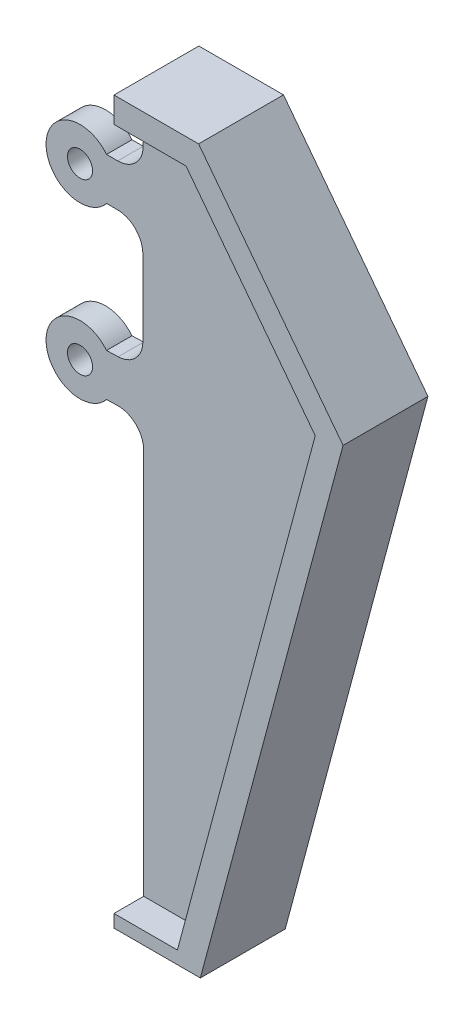
SolidWorks part; units mm, degrees
ref_plane "Front Plane" through (0, 0, 0) normal (0, 0, 1) x (1, 0, 0)
ref_plane "Top Plane" through (0, 0, 0) normal (0, 1, 0) x (1, 0, 0)
ref_plane "Right Plane" through (0, 0, 0) normal (1, 0, 0) x (0, 0, -1)
sketch "Sketch1" plane through (0, 0, 0) normal (0, 0, 1) x (1, 0, 0)
  line L0 (57.8544, 21.5204) -> (66.3427, 21.5204)
  line L1 (66.3427, 21.5204) -> (81.5634, 1.6159)
  line L2 (81.5634, 1.6159) -> (64.9249, -60.4796)
  line L9 (57.8544, 24.5204) -> (67.8253, 24.5204)
  line L11 (67.8253, 24.5204) -> (84.8432, 2.2654)
  line L16 (84.8432, 2.2654) -> (68.0307, -60.4796)
  line L26 (57.8544, 21.5204) -> (57.8544, 24.5204)
  line L27 (64.9249, -60.4796) -> (68.0307, -60.4796)
  line L29 (54.896, 24.5204) -> (67.8253, 24.5204) construction
  line L30 (54.7981, 17.5204) -> (54.896, 24.5204) construction
  line L31 (50.4769, 17.5204) -> (54.7981, 17.5204) construction
  line L32 (50.4769, 6.5204) -> (50.4769, 17.5204) construction
  line L33 (54.7565, 6.5204) -> (50.4769, 6.5204) construction
  line L34 (54.7565, -2.4381) -> (54.7565, 6.5204) construction
  line L35 (50.4769, -2.5721) -> (54.7565, -2.4381) construction
  line L36 (50.4769, -13.5447) -> (50.4769, -2.5721) construction
  line L37 (54.8544, -63.4796) -> (54.8544, -13.4508) construction
  line L38 (54.8544, -13.4508) -> (50.4769, -13.5447) construction
  line L39 (84.8432, 2.2654) -> (67.2269, -63.4796) construction
  line L40 (67.2269, -63.4796) -> (54.8544, -63.4796) construction
  line L41 (57.7565, -5.3456) -> (57.7565, 9.5204) construction
  line L42 (53.4769, -5.4796) -> (57.7565, -5.3456) construction
  line L43 (57.7565, 9.5204) -> (53.4769, 9.5204) construction
  line L44 (57.8544, -10.3857) -> (53.4769, -10.4796) construction
  line L45 (57.8544, -60.4796) -> (57.8544, -10.3857) construction
  line L46 (53.4769, -10.4796) -> (53.4769, -5.4796) construction
  line L47 (57.7565, 14.5204) -> (57.8544, 21.5204) construction
  line L48 (53.4769, 9.5204) -> (53.4769, 14.5204) construction
  line L49 (53.4769, 14.5204) -> (57.7565, 14.5204) construction
  line L50 (64.9249, -60.4796) -> (57.8544, -60.4796) construction
extrude "Boss-Extrude4" add sketch "Sketch1" along normal blind 5 and the other way blind 5
sketch "Sketch4" plane through (0, 0, 0) normal (0, 0, 1) x (1, 0, 0)
  line L0 (57.8542, 21.5184) -> (66.3426, 21.5184)
  line L1 (66.3426, 21.5184) -> (81.5632, 1.6139)
  line L2 (81.5632, 1.6139) -> (64.9248, -60.4816)
  line L3 (64.9248, -60.4816) -> (57.8542, -60.4816)
  line L4 (57.8542, -60.4816) -> (57.8542, -13.4528)
  line L6 (54.7899, -10.4534) -> (53.4767, -10.4816)
  line L8 (53.4767, -5.4816) -> (54.8502, -5.4386)
  line L10 (57.7563, -2.4401) -> (57.7563, 6.5184)
  line L12 (54.7563, 9.5184) -> (53.4767, 9.5184)
  line L14 (53.4767, 14.5184) -> (54.798, 14.5184)
  line L15 (57.7977, 17.4764) -> (57.8542, 21.5184)
  arc A0 (53.4767, 14.5184) -> (53.4767, 9.5184) centre (50.3542, 12.0184) ccw
  arc A1 (53.4767, -5.4816) -> (53.4767, -10.4816) centre (50.3542, -7.9816) ccw
  arc A2 (57.8542, -13.4528) -> (54.7899, -10.4534) centre (54.8542, -13.4528) ccw
  arc A3 (57.7563, -2.4401) -> (54.8502, -5.4386) centre (54.7563, -2.4401) cw
  arc A4 (57.7563, 6.5184) -> (54.7563, 9.5184) centre (54.7563, 6.5184) ccw
  arc A5 (54.798, 14.5184) -> (57.7977, 17.4764) centre (54.798, 17.5184) ccw
extrude "Boss-Extrude8" add sketch "Sketch4" along normal blind 1.5 and the other way blind 1.5 separate body
sketch "Sketch6" plane through (0, 0, 1.5) normal (0, 0, 1) x (1, 0, 0)
  line L0 (57.8542, -60.4816) -> (57.8542, -58.9816)
  line L1 (57.8542, -13.4528) -> (57.8542, -60.4816) construction
  line L2 (57.8542, -58.9816) -> (65.3267, -58.9816)
  line L3 (64.9248, -60.4816) -> (81.5632, 1.6139) construction
  line L4 (65.3267, -58.9816) -> (64.9249, -60.4796)
  line L5 (64.9249, -60.4796) -> (57.8542, -60.4816)
extrude "Boss-Extrude9" add sketch "Sketch6" along normal up to vertex (3.5 mm away) and the other way up to vertex (6.5 mm away) up to point (64.9249, -60.4796, 5) other way up to point (64.9249, -60.4796, -5)
sketch "Sketch7" plane through (0, 0, 1.5) normal (0, 0, 1) x (1, 0, 0)
  circle A0 centre (50.3542, -7.9816) radius 1.48
extrude "Cut-Extrude4" cut sketch "Sketch7" against normal up to vertex (3 mm away) up to point (53.4767, -5.4816, -1.5)
sketch "Sketch8" plane through (0, 0, 1.5) normal (0, 0, 1) x (1, 0, 0)
  circle A0 centre (50.3542, 12.0184) radius 1.48
extrude "Cut-Extrude5" cut sketch "Sketch8" against normal up to vertex (3 mm away) up to point (53.4767, 14.5184, -1.5)
